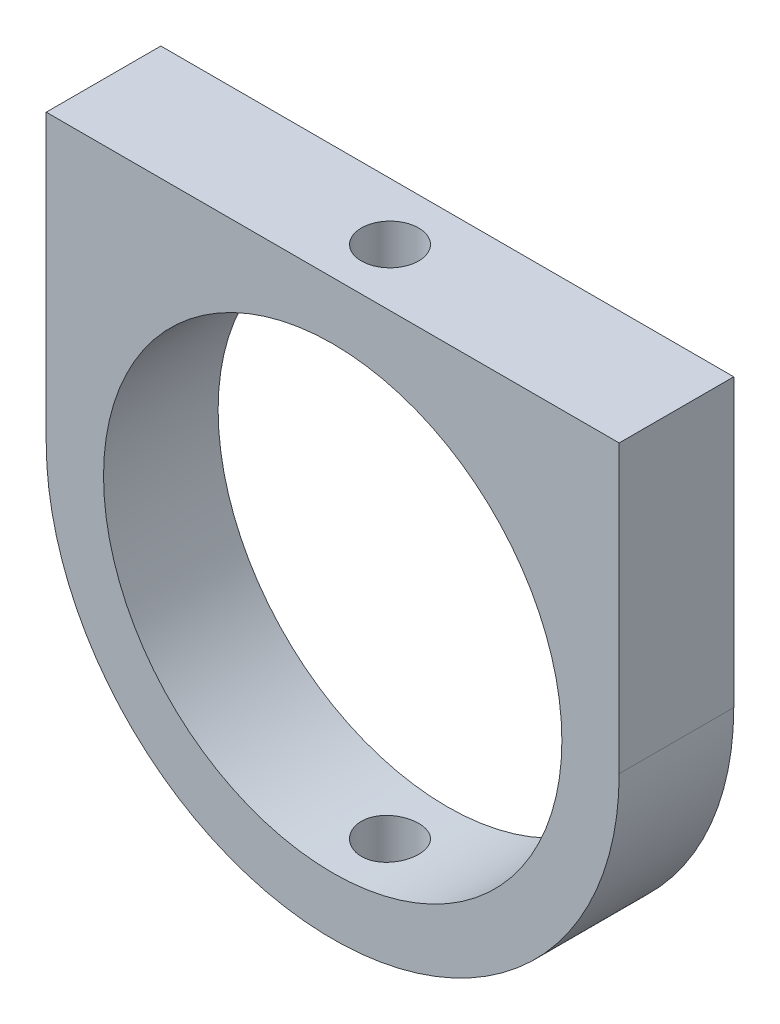
SolidWorks part; units mm, degrees
material "6063-T5"
ref_plane "Front Plane" through (0, 0, 0) normal (0, 0, 1) x (1, 0, 0)
ref_plane "Top Plane" through (0, 0, 0) normal (0, 1, 0) x (1, 0, 0)
ref_plane "Right Plane" through (0, 0, 0) normal (1, 0, 0) x (0, 0, -1)
sketch "Sketch1" plane through (0, 0, 0) normal (0, 0, 1) x (1, 0, 0)
  line L1 (-10, -10) -> (10, -10)
  line L2 (-10, -10) -> (-10, 10)
  line L3 (-10, 10) -> (10, 10)
  line L4 (10, -10) -> (10, 10)
  line L5 (-10, -10) -> (10, 10) construction
  line L6 (-10, 10) -> (10, -10) construction
  circle A0 centre (0, 0) radius 8
  arc A1 (-10, 0) -> (10, 0) centre (0, 0) ccw
  point P0 (0, 0)
extrude "Boss-Extrude1" add sketch "Sketch1" along normal blind 4 contours L2 A1 L4 L3 A0 region at (-6.8711, -6.8711, 0)
sketch "Sketch3" plane through (0, 10, 0) normal (0, 1, 0) x (1, 0, 0)
  circle A0 centre (0, -2) radius 1
extrude "Cut-Extrude1" cut sketch "Sketch3" against normal blind 20
